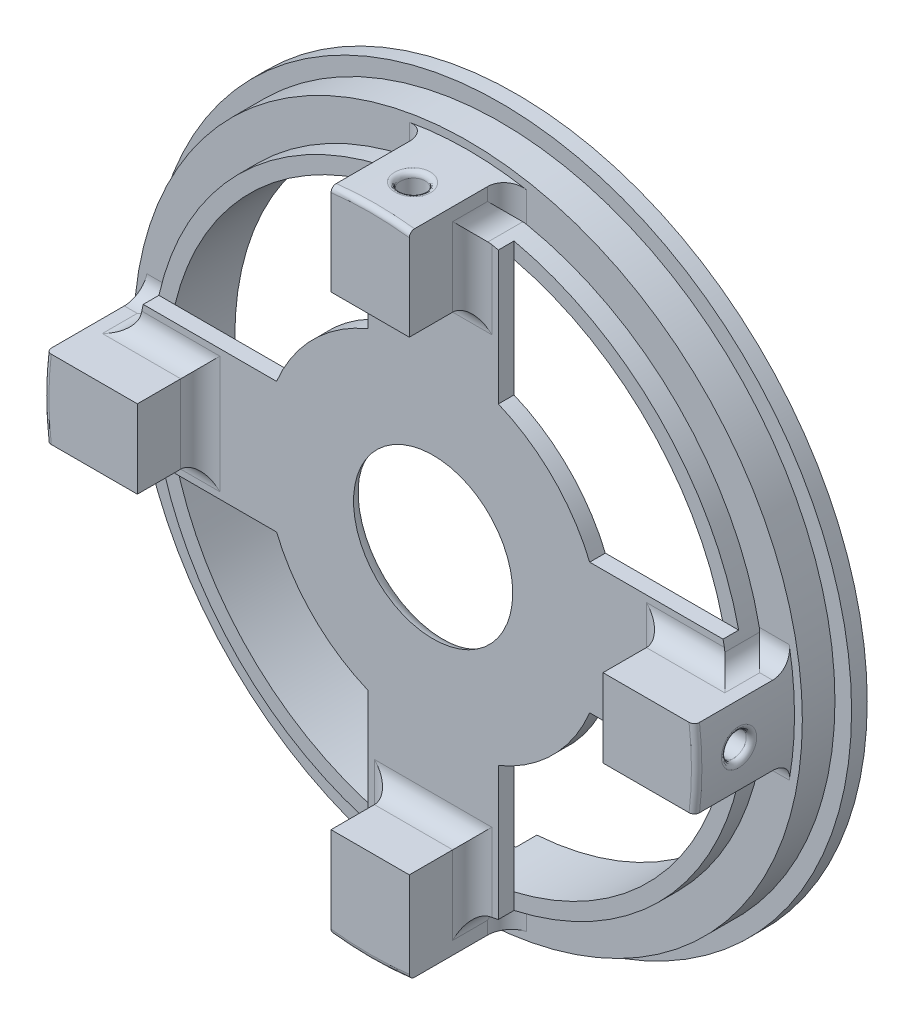
SolidWorks part; units mm, degrees
ref_plane "Front Plane" through (0, 0, 0) normal (0, 0, 1) x (1, 0, 0)
ref_plane "Top Plane" through (0, 0, 0) normal (0, 1, 0) x (1, 0, 0)
ref_plane "Right Plane" through (0, 0, 0) normal (1, 0, 0) x (0, 0, -1)
sketch "Sketch1" plane through (0, 0, 0) normal (0, 0, 1) x (1, 0, 0)
  circle A0 centre (0, 0) radius 53.8 construction
  circle A1 centre (0, 0) radius 53.8
  circle A4 centre (0, 0) radius 43.15
  circle A5 centre (0, 0) radius 43.15
extrude "Boss-Extrude1" add sketch "Sketch1" along normal blind 2.4
sketch "Sketch6" plane through (0, 0, 10.2) normal (0, 0, 1) x (1, 0, 0)
  circle A2 centre (0, 0) radius 43.15 construction
  circle A3 centre (0, 0) radius 43.15
extrude "Boss-Extrude4" add sketch "Sketch6" along normal blind 2.4 from offset 0.15 separate body
sketch "Sketch7" plane through (0, 0, 2.4) normal (0, 0, 1) x (1, 0, 0)
  circle A0 centre (0, 0) radius 43.15 construction
  circle A1 centre (0, 0) radius 43.15
extrude "Extrude-Thin2" add sketch "Sketch7" along normal up to surface (10.35 mm away) thin up to face at (43.15, 0, 12.75) thin type one direction wall 2.4
sketch "Sketch9" plane through (0, 0, 12.75) normal (0, 0, 1) x (1, 0, 0)
  circle A2 centre (0, 0) radius 12.2
  circle A3 centre (0, 0) radius 12.2
  dimension "D1" = 0.2
extrude "Cut-Extrude1" cut sketch "Sketch9" against normal up to surface (2.4 mm away) up to face at (43.15, 0, 10.35)
sketch "Sketch10" plane through (0, 0, 12.75) normal (0, 0, 1) x (1, 0, 0)
  line L0 (0, -45.55) -> (0, 45.55) construction
  line L1 (45.55, 0) -> (-45.55, 0) construction
  line L2 (10, -44.4387) -> (10, 44.4387)
  line L3 (44.4387, -10) -> (-44.4387, -10)
  line L4 (44.4387, 10) -> (-44.4387, 10)
  line L5 (-10, -44.4387) -> (-10, 44.4387)
  circle A0 centre (0, 0) radius 45.55 construction
  circle A1 centre (0, 0) radius 45.55
  circle A2 centre (0, 0) radius 26
  point P9 (10, 0)
  point P12 (0, -10)
  circle M7 centre (0, 0) radius 45.55
  dimension "D3" = 52
  dimension "D1" = 10
  dimension "D2" = 10
extrude "Cut-Extrude2" cut sketch "Sketch10" against normal up to surface (2.4 mm away) contours A2 L2 L3 M7 | A2 L3 L5 M7 | A2 L5 L4 M7 | A2 L4 L2 M7 region at (25.148, -25.148, 12.75) region at (-25.148, -25.148, 12.75) region at (-25.148, 25.148, 12.75) region at (25.148, 25.148, 12.75) up to face at (12.2, 0, 10.35)
sketch "Sketch8" plane through (0, 0, 2.4) normal (0, 0, 1) x (1, 0, 0)
  circle A2 centre (0, 0) radius 45.55 construction
  circle A3 centre (0, 0) radius 45.55
  circle A6 centre (0, 0) radius 51.25
  circle A7 centre (0, 0) radius 51.25
  dimension "D1" = 2.55
extrude "Boss-Extrude5" add sketch "Sketch8" along normal blind 5
sketch "Sketch12" plane through (0, 0, 7.4) normal (0, 0, 1) x (1, 0, 0)
  line L0 (0, 0) -> (-50.05, 0) construction
  line L1 (-49.6891, -6) -> (-35.6891, -6)
  line L2 (-35.6891, -6) -> (-35.6891, 6)
  line L3 (-49.6891, 6) -> (-35.6891, 6)
  circle A2 centre (0, 0) radius 50.05
  circle A3 centre (0, 0) radius 50.05
  point P8 (-35.6891, 0)
  circle M6 centre (0, 0) radius 45.55
  dimension "D2" = 6
  dimension "D3" = 14
  dimension "D1" = 1.2
extrude "Boss-Extrude6" add sketch "Sketch12" along normal blind 15 contours L2 L0 L1 M6 | L0 L2 L3 M6 | L0 A3 L1 M6 | L0 L3 A3 M6 region at (-40.5542, -2.9796, 7.4) region at (-40.5542, 2.9796, 7.4) region at (-47.6736, -3.004, 7.4) region at (-47.6736, 3.004, 7.4)
sketch "Sketch14" plane through (0, 0, 7.4) normal (0, 0, -1) x (-1, 0, 0)
  line L3 (42.7308, 6) -> (35.6891, 6)
  line L4 (35.6891, 6) -> (35.6891, -6)
  line L5 (35.6891, -6) -> (42.7308, -6)
  line L6 (42.7308, 6) -> (35.6891, 6)
  line L7 (35.6891, 6) -> (35.6891, -6)
  line L8 (35.6891, -6) -> (42.7308, -6)
  arc A1 (42.7308, -6) -> (42.7308, 6) centre (0, 0) ccw
  arc A2 (42.7308, -6) -> (42.7308, 6) centre (0, 0) ccw
  dimension "D1" = 0
extrude "Cut-Extrude4" cut sketch "Sketch14" against normal up to surface (2.95 mm away) up to face at (-7.788, 0, 10.35)
sketch "Sketch13" plane through (-35.6891, 0, 0) normal (1, 0, 0) x (0, 0, -1)
  line L0 (-22.4, -6) -> (-22.4, 6) construction
  circle A0 centre (-15.9, 0) radius 1.9
  point P2 (-22.4, 0)
  dimension "D1" = 3.8
  dimension "D2" = 6.5
extrude "Cut-Extrude3" cut sketch "Sketch13" against normal through all from offset 5 offset against normal yes
fillet "Fillet1" radius 3 7 edges at (-35.6891, 0, 12.75) (-40.4211, -6, 12.75) (-45.1531, -6, 10.075) (-45.1531, 6, 10.075) (-40.4211, 6, 12.75) (-47.4211, -6, 7.4) (-47.4211, 6, 7.4)
fillet "Fillet2" radius 0.8 2 edges at (-50.05, 0, 22.4) (-50.0481, -0.4355, 17.7494)
pattern_circular "CirPattern4" count 4 over 360 about axis through (0, 0, 141.5849) along (0, 0, -1) of "Boss-Extrude6", "Cut-Extrude4", "Cut-Extrude3", "Fillet1", "Fillet2"
sketch "Sketch17" plane through (0, 0, 0) normal (0, 0, -1) x (-1, 0, 0)
  circle A0 centre (0, 0) radius 43.15 construction
  circle A1 centre (0, 0) radius 43.15
  ellipse E0 centre (0, 43) end of major axis (0, 39.2) minor radius 3 (2.9989, 42.8953) -> (-2.9989, 42.8953) ccw construction
  ellipse E1 centre (0, -43) end of major axis (0, -39.2) minor radius 3 (-2.9989, -42.8953) -> (2.9989, -42.8953) ccw construction
  ellipse E2 centre (0, 43) end of major axis (0, 39.2) minor radius 3 (2.9989, 42.8953) -> (-2.9989, 42.8953) ccw
  ellipse E3 centre (0, -43) end of major axis (0, -39.2) minor radius 3 (-2.9989, -42.8953) -> (2.9989, -42.8953) ccw
  spline S0 degree 1 poles (-3.1488, -42.892) (3.1488, -42.892) knots 0 0 1 1 construction
  spline S1 degree 3 poles (-3.1488, -42.892) (-3.1601, -43.4079) (-3.0156, -44.4646) (-2.1068, -46.2652) (0, -47.4065) (2.1068, -46.2652) (3.0156, -44.4646) (3.1601, -43.4079) (3.1488, -42.892) knots 1.54324 1.54324 1.54324 1.54324 1.942828 2.342417 3.141593 3.940769 4.340357 4.739945 4.739945 4.739945 4.739945
  spline S2 degree 1 poles (3.1488, 42.892) (-3.1488, 42.892) knots 0 0 1 1 construction
  spline S3 degree 3 poles (3.1488, 42.892) (3.1601, 43.4079) (3.0156, 44.4646) (2.1068, 46.2652) (0, 47.4065) (-2.1068, 46.2652) (-3.0156, 44.4646) (-3.1601, 43.4079) (-3.1488, 42.892) knots 1.54324 1.54324 1.54324 1.54324 1.942828 2.342417 3.141593 3.940769 4.340357 4.739945 4.739945 4.739945 4.739945
  circle M3 centre (0, 0) radius 43.15
extrude "Cut-Extrude5" cut sketch "Sketch17" against normal blind 3.2 contours E2 M3 | A1 S3 E2 | E3 M3 | A1 S1 E3 M3 region at (-3.0801, 43.1143, 0) region at (0, -46.8758, 0) region at (0, 44.6747, 0) region at (0, -44.6747, 0)
fillet "Fillet3" radius 3 1 edges at (12.2, 0, 10.35)
equation "\"D1@Boss-Extrude1\"=\"Wall thickness@BOX_PLAYERS.Assembly\""
equation "\"D1@Sketch1\"=\"Gap@BOX_PLAYERS.Assembly\""
equation "\"D1@Boss-Extrude4\"=\"Wall thickness@BOX_PLAYERS.Assembly\""
equation "\"D19@Boss-Extrude4\"=\"Gap@BOX_PLAYERS.Assembly\""
equation "\"D5@Extrude-Thin2\"=\"Wall thickness@BOX_PLAYERS.Assembly\""
equation "\"D1@Sketch8\"=\"Wall thickness@BOX_PLAYERS.Assembly\"+\"Gap@BOX_PLAYERS.Assembly\""
equation "\"D1@Sketch12\"=\"Body thickening@BOX_PLAYERS.Assembly\""
equation "\"D1@Sketch13\"=\"Sleeve@BOX_PLAYERS.Assembly\""
equation "\"D1@Sketch17\"=\"Gap@BOX_PLAYERS.Assembly\""
